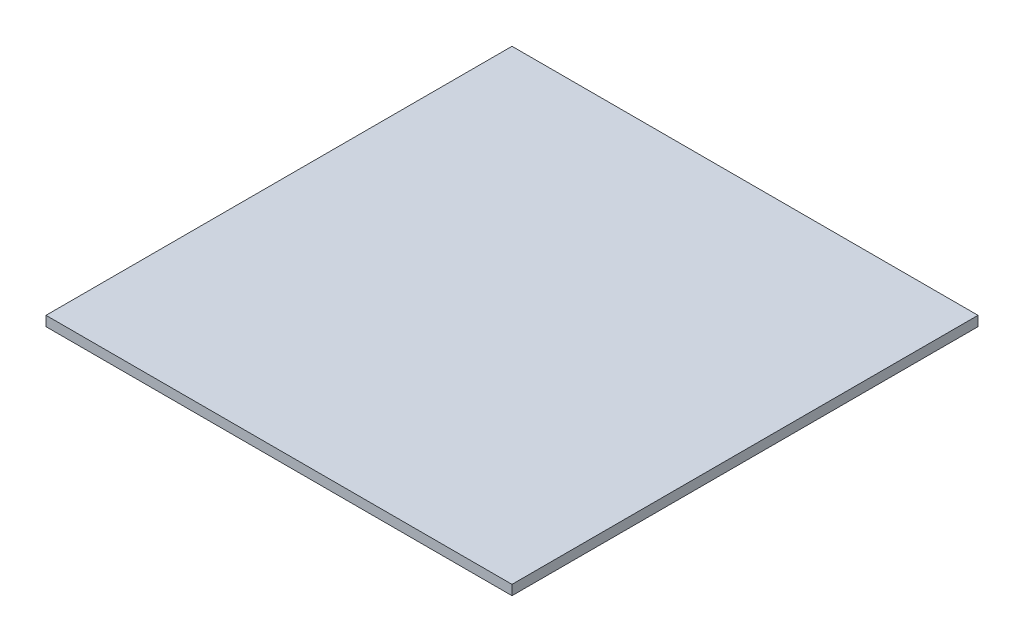
SolidWorks part; units mm, degrees
material "Acrylic (Medium-high impact)"
ref_plane "Front" through (0, 0, 0) normal (0, 0, 1) x (1, 0, 0)
ref_plane "Top" through (0, 0, 0) normal (0, 1, 0) x (1, 0, 0)
ref_plane "Right" through (0, 0, 0) normal (1, 0, 0) x (0, 0, -1)
sketch "Sketch1" plane through (0, 0, 0) normal (0, 1, 0) x (1, 0, 0)
  line L1 (0, -149.873) -> (299.746, -149.873)
  line L2 (0, -149.873) -> (0, 149.873)
  line L3 (0, 149.873) -> (299.746, 149.873)
  line L4 (299.746, -149.873) -> (299.746, 149.873)
  point P6 (0, 0)
  dimension "D1" = 299.746
  dimension "D2" = 299.746
extrude "Boss-Extrude1" add sketch "Sketch1" along normal blind 6.35
other "PropertyManager" [suppressed]
equation "\"thick\"= .25in"
equation "\"tol\"= .005in"
equation "\"ftprnt\"= 30cm"
equation "\"D1@Sketch1\"=\"ftprnt\"-(\"tol\"*2)"
equation "\"D1@Boss-Extrude1\"=\"thick\""
equation "\"height\"= 5cm"
equation "\"D2@Sketch1\"=\"ftprnt\"-(\"tol\"*2)"
